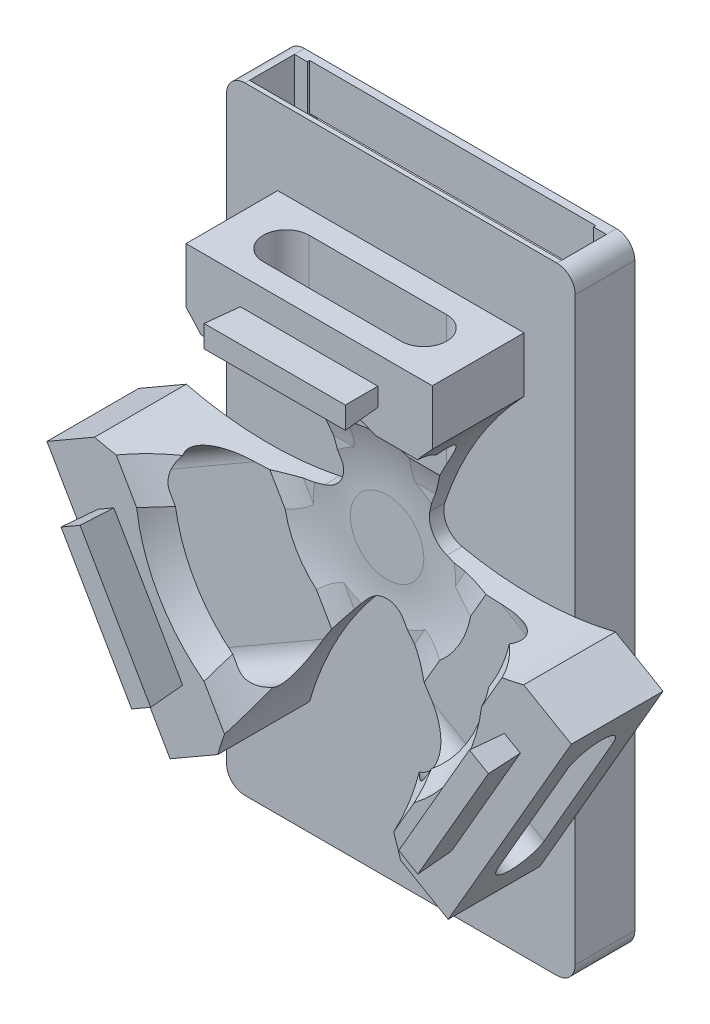
SolidWorks part; units mm, degrees
ref_plane "Plano frontal" through (0, 0, 0) normal (0, 0, 1) x (1, 0, 0)
ref_plane "Plano superior" through (0, 0, 0) normal (0, 1, 0) x (1, 0, 0)
ref_plane "Plano direito" through (0, 0, 0) normal (1, 0, 0) x (0, 0, -1)
sketch "Esboço1" plane through (0, 0, 0) normal (0, 0, 1) x (1, 0, 0)
  line L38 (26.8468, 46.5) -> (26.8468, 38.5)
  line L39 (-26.8468, 38.5) -> (-26.8468, 46.5)
  line L40 (-53.6936, 0) -> (-46.7654, 4)
  line L41 (-26.8468, -46.5) -> (-19.9186, -42.5)
  line L42 (26.8468, -46.5) -> (19.9186, -42.5)
  line L43 (46.7654, 4) -> (53.6936, 0)
  line L44 (26.8468, 46.5) -> (26.8468, 50.5)
  line L45 (26.8468, 50.5) -> (-26.8468, 50.5)
  line L46 (-26.8468, 46.5) -> (-26.8468, 50.5)
  line L47 (-53.6936, 0) -> (-57.1577, -2)
  line L48 (-57.1577, -2) -> (-30.3109, -48.5)
  line L49 (-26.8468, -46.5) -> (-30.3109, -48.5)
  line L50 (26.8468, -46.5) -> (30.3109, -48.5)
  line L51 (30.3109, -48.5) -> (57.1577, -2)
  line L52 (53.6936, 0) -> (57.1577, -2)
  arc A10 (-26.8468, 38.5) -> (-9.603, 9.8434) centre (-80.7333, -13.442) cw
  arc A12 (26.8468, 38.5) -> (9.603, 9.8434) centre (80.7333, -13.442) ccw
  arc A13 (-19.9186, -42.5) -> (-3.7231, -13.2381) centre (52.0077, -63.1961) cw
  arc A14 (-46.7654, 4) -> (-13.3261, 3.3948) centre (-28.7255, 76.6381) ccw
  arc A18 (19.9186, -42.5) -> (3.7231, -13.2381) centre (-52.0077, -63.1961) ccw
  arc A20 (46.7654, 4) -> (13.3261, 3.3948) centre (28.7255, 76.6381) cw
  arc A25 (-9.603, 9.8434) -> (-13.3261, 3.3948) centre (-14.3549, 8.2878) cw
  arc A26 (13.3261, 3.3948) -> (9.603, 9.8434) centre (14.3549, 8.2878) cw
  arc A27 (3.7231, -13.2381) -> (-3.7231, -13.2381) centre (0, -16.5756) ccw
  dimension "D1" = 5
  dimension "D2" = 5
  dimension "D3" = 5
extrude "Ressalto-extrusão1" add sketch "Esboço1" along normal blind 20
sketch "Esboço2" plane through (0, 0, 20) normal (0, 0, 1) x (1, 0, 0)
  line L2 (0, 44.5) -> (-15, 44.5)
  line L5 (0, 44.5) -> (15, 44.5)
  line L9 (-15, 44.5) -> (-15, 42)
  line L10 (15, 44.5) -> (15, 42)
  line L11 (-15, 42) -> (-15, 40.5)
  line L13 (-38.5381, -22.25) -> (-31.0381, -35.2404)
  line L20 (-38.5381, -22.25) -> (-46.0381, -9.2596)
  line L21 (-31.0381, -35.2404) -> (-28.8731, -33.9904)
  line L22 (-46.0381, -9.2596) -> (-43.8731, -8.0096)
  line L23 (-15, 40.5) -> (15, 40.5)
  line L24 (38.5381, -22.25) -> (46.0381, -9.2596)
  line L26 (38.5381, -22.25) -> (31.0381, -35.2404)
  line L27 (46.0381, -9.2596) -> (43.8731, -8.0096)
  line L28 (31.0381, -35.2404) -> (28.8731, -33.9904)
  line L29 (15, 42) -> (15, 40.5)
  line L30 (-28.8731, -33.9904) -> (-27.574, -33.2404)
  line L31 (-27.574, -33.2404) -> (-42.574, -7.2596)
  line L32 (-43.8731, -8.0096) -> (-42.574, -7.2596)
  line L33 (43.8731, -8.0096) -> (42.574, -7.2596)
  line L34 (42.574, -7.2596) -> (27.574, -33.2404)
  line L35 (28.8731, -33.9904) -> (27.574, -33.2404)
extrude "Ressalto-extrusão2" add sketch "Esboço2" along normal blind 7.5 draft 3 draft outward yes
sketch "Esboço3" plane through (0, 0, 0) normal (0, 0, -1) x (-1, 0, 0)
  line L0 (38, 63.2507) -> (38, -63.2507)
  line L1 (-34, -67.2507) -> (34, -67.2507)
  line L2 (-34, 67.2507) -> (34, 67.2507)
  line L3 (-38, 63.2507) -> (-38, -63.2507)
  arc A0 (38, 63.2507) -> (34, 67.2507) centre (34, 63.2507) ccw
  arc A1 (-34, 67.2507) -> (-38, 63.2507) centre (-34, 63.2507) ccw
  arc A2 (-38, -63.2507) -> (-34, -67.2507) centre (-34, -63.2507) ccw
  arc A3 (34, -67.2507) -> (38, -63.2507) centre (34, -63.2507) ccw
extrude "Ressalto-extrusão3" add sketch "Esboço3" along normal blind 13
sketch "Esboço4" plane through (0, 67.2507, 0) normal (0, 1, 0) x (1, 0, 0)
  line L0 (34.2, 1) -> (-34.2, 1)
  line L1 (0, 1) -> (0, 0)
  line L2 (34.2, 1) -> (34.2, 10.3)
  line L3 (-34.2, 1) -> (-34.2, 10.3)
  line L7 (31.2, 10.8) -> (31.2, 11.3)
  line L8 (-31.2, 10.8) -> (-31.2, 11.3)
  line L9 (31.2, 10.8) -> (34.2, 10.8)
  line L11 (-31.2, 11.3) -> (31.2, 11.3)
  line L12 (-34.2, 10.8) -> (-31.2, 10.8)
  line L13 (-34.2, 10.3) -> (-34.2, 10.8)
  line L14 (34.2, 10.3) -> (34.2, 10.8)
  line M10 (34, 0) -> (34, 13)
  line M11 (34, 13) -> (-34, 13)
  line M12 (-34, 13) -> (-34, 0)
extrude "Corte-extrusão1" cut sketch "Esboço4" against normal blind 131 contours L8 L0 L7 M12 M10 M11 | L8 L7 M11 region at (0, 67.2507, -6.1303)
sketch "Esboço6" plane through (-26.8468, 0, 0) normal (-1, 0, 0) x (0, 0, 1)
  line L1 (20.0435, 34.9447) -> (31.5599, 34.9447)
  line L4 (3.5763, 4) -> (3.5763, 14)
  line L7 (3.5763, 4) -> (21.2226, 4)
  line L9 (21.2226, 4) -> (31.5599, 34.9447)
  arc A2 (3.5763, 14) -> (20.0435, 34.9447) centre (30.4192, 9.8413) cw
extrude "Corte-extrusão2" cut sketch "Esboço6" against normal blind 60
sketch "Esboço8" plane through (13.4234, -23.25, 0) normal (0.5, -0.866, 0) x (0.866, 0.5, 0)
  line L0 (-34.9447, 20.0435) -> (-34.9447, 31.5599)
  line L1 (-4, 3.5763) -> (-14, 3.5763)
  line L5 (-4, 3.5763) -> (-4, 21.2226)
  line L7 (-4, 21.2226) -> (-34.9447, 31.5599)
  arc A2 (-14, 3.5763) -> (-34.9447, 20.0435) centre (-9.8413, 30.4192) cw
extrude "Corte-extrusão3" cut sketch "Esboço8" against normal blind 58
sketch "Esboço10" plane through (13.4234, 23.25, 0) normal (0.5, 0.866, 0) x (0.866, -0.5, 0)
  line L1 (34.9447, -20.0435) -> (34.9447, -31.5599)
  line L6 (4, -3.5763) -> (14, -3.5763)
  line L8 (4, -3.5763) -> (4, -21.2226)
  line L10 (4, -21.2226) -> (34.9447, -31.5599)
  arc A2 (14, -3.5763) -> (34.9447, -20.0435) centre (9.8413, -30.4192) cw
extrude "Corte-extrusão4" cut sketch "Esboço10" against normal blind 53
sketch "Esboço15" plane through (0, 0, 0) normal (1, 0, 0) x (0, 0, -1)
  line L0 (-62.7505, 34.8879) -> (-62.7505, 37.8879)
  line L2 (-62.7505, 34.8879) -> (-62.7505, 0)
  line L3 (-3, 0) -> (-62.7505, 0)
  line L4 (-62.7505, 37.8879) -> (-20, 37.8879)
  line L5 (-3, 0) -> (-3, 8)
  arc A1 (-20, 37.8879) -> (-3, 8) centre (-35.5517, 9.2635) cw
revolve "Corte-Revolução2" cut sketch "Esboço15" angle 360 about L3
sketch "Esboço12" plane through (0, 67.2507, 0) normal (0, 1, 0) x (1, 0, 0)
  line L0 (-31.2, 11.3) -> (-31.2, 13)
  line L1 (-34, 13) -> (34, 13) construction
  line L2 (31.2, 11.3) -> (31.2, 13)
sketch "Esboço13" plane through (0, 0, -13) normal (0, 0, -1) x (-1, 0, 0)
  line L0 (-31.2, 57.2507) -> (-31.2, 5)
  line L1 (31.2, 57.2507) -> (31.2, 5)
  line L2 (-31.2, -63.7493) -> (31.2, -63.7493)
  line L6 (-31.2, 57.2507) -> (31.2, 57.2507)
  line L17 (-31.2, 5) -> (31.2, 5)
  line L18 (-31.2, -5) -> (-31.2, -63.7493)
  line L19 (31.2, -5) -> (31.2, -63.7493)
  line L20 (-31.2, -5) -> (31.2, -5)
extrude "Corte-extrusão6" cut sketch "Esboço13" against normal blind 3.4
sketch "Esboço16" plane through (-43.7343, -25.25, 0) normal (-0.866, -0.5, 0) x (0, 0, 1)
  line L5 (10, -15) -> (10, 15) construction
  line L6 (5, -15) -> (5, 15)
  line L9 (15, -15) -> (15, 15)
  arc A0 (5, -15) -> (15, -15) centre (10, -15) ccw
  arc A1 (15, 15) -> (5, 15) centre (10, 15) ccw
  point P6 (10, 0)
extrude "Corte-extrusão8" cut sketch "Esboço16" against normal blind 42
sketch "Esboço18" plane through (43.7343, -25.25, 0) normal (0.866, -0.5, 0) x (0, 0, -1)
  line L2 (-10, 15) -> (-10, -15) construction
  line L3 (-5, 15) -> (-5, -15)
  line L4 (-15, 15) -> (-15, -15)
  arc A0 (-5, 15) -> (-15, 15) centre (-10, 15) ccw
  arc A1 (-15, -15) -> (-5, -15) centre (-10, -15) ccw
  point P7 (-10, 0)
extrude "Corte-extrusão9" cut sketch "Esboço18" against normal blind 42 contours L4 A1 L3 A0
sketch "Esboço19" plane through (0, 50.5, 0) normal (0, 1, 0) x (1, 0, 0)
  line L2 (-15, -10) -> (15, -10) construction
  line L3 (-15, -5) -> (15, -5)
  line L4 (-15, -15) -> (15, -15)
  arc A0 (-15, -5) -> (-15, -15) centre (-15, -10) ccw
  arc A1 (15, -15) -> (15, -5) centre (15, -10) ccw
  point P7 (0, -10)
extrude "Corte-extrusão10" cut sketch "Esboço19" against normal blind 42 contours L4 A1 L3 A0
